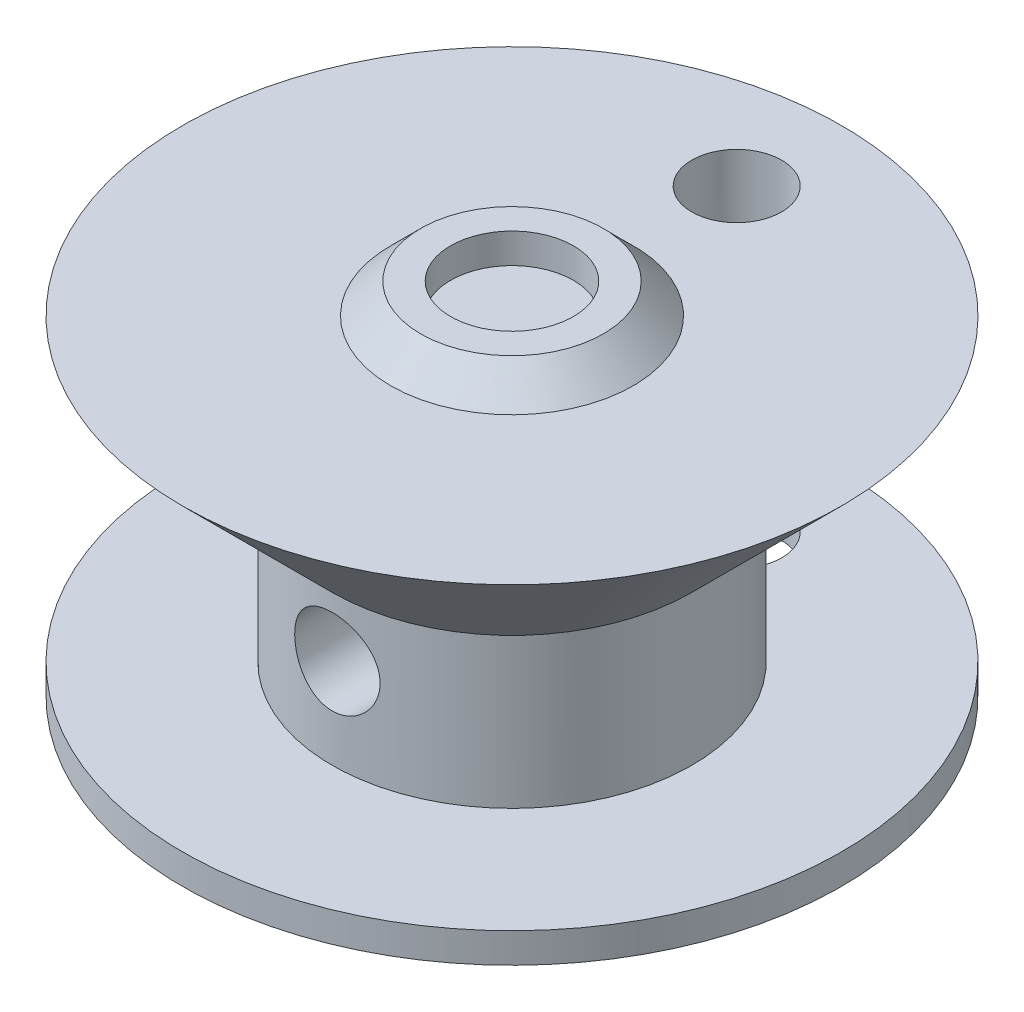
SolidWorks part; units mm, degrees
material "ABS"
ref_plane "Front Plane" through (0, 0, 0) normal (0, 0, 1) x (1, 0, 0)
ref_plane "Top Plane" through (0, 0, 0) normal (0, 1, 0) x (1, 0, 0)
ref_plane "Right Plane" through (0, 0, 0) normal (1, 0, 0) x (0, 0, -1)
sketch "Sketch1" plane through (0, 0, 0) normal (1, 0, 0) x (0, 0, -1)
  line L0 (0, 6) -> (-11, 6) construction
  line L1 (0, 0) -> (0, 18.3424) construction
  line L2 (-11, 6) -> (-11, -6) construction
  line L3 (-11, -6) -> (0, -6) construction
  line L4 (0, -6) -> (0, 6) construction
  line L5 (-11, 6) -> (-11, 5)
  line L7 (-6, 0) -> (-6, -5)
  line L9 (-11, -5) -> (-11, -6)
  line L10 (-11, -6) -> (0, -6) construction
  line L11 (0, -6) -> (0, 6) construction
  line L12 (0, 6) -> (-11, 6) construction
  line L13 (-11, 5) -> (-6, 0)
  line L14 (-6, 0) -> (-6, 6) construction
  line L15 (-11, -5) -> (-6, -5)
  line L16 (-11, 6) -> (-2, 6)
  line L17 (2, -6) -> (-2, -6) construction
  line L18 (2, -6) -> (2, 6) construction
  line L19 (2, 6) -> (-2, 6) construction
  line L20 (-2, -6) -> (-2, 6) construction
  line L21 (2, -6) -> (-2, 6) construction
  line L22 (2, 6) -> (-2, -6) construction
  line L23 (-2.05, 5) -> (2.05, 5) construction
  line L24 (-2.05, 5) -> (-2.05, 7) construction
  line L25 (-2.05, 7) -> (2.05, 7) construction
  line L26 (2.05, 5) -> (2.05, 7) construction
  line L27 (-2.05, 5) -> (2.05, 7) construction
  line L28 (-2.05, 7) -> (2.05, 5) construction
  line L30 (-2.05, 5) -> (0, 5)
  line L31 (0, 5) -> (0, -6) construction
  line L33 (-2, 2) -> (-2, -6)
  line L34 (-2, -6) -> (-11, -6)
  line L35 (-2, 2) -> (0, 4)
  line L36 (0, 4) -> (0, 5)
  line L37 (-2.05, 5) -> (-2.05, 6)
  line L38 (-2.05, 6) -> (-2, 6)
  point P3 (0, 0)
  point P16 (0, 0)
  dimension "D1" = 22
  dimension "D2" = 8
  dimension "D3" = 45
  dimension "D4" = 1
  dimension "D5" = 5
  dimension "D6" = 4
  dimension "D7" = 4
  dimension "D8" = 4.1
  dimension "D9" = 1
  dimension "D10" = 45
  dimension "D11" = 12
revolve "Spool Solid" add sketch "Sketch1" angle 360 about L1 region at (0, 0.7664, 5.0692)
sketch "Sketch2" plane through (0, -6, 0) normal (0, -1, 0) x (1, 0, 0)
  line L0 (1.3229, 1.5) -> (-1.3229, 1.5)
  circle A2 centre (0, 0) radius 2 construction
  circle A3 centre (0, 0) radius 2 construction
  arc A4 (1.3229, 1.5) -> (-1.3229, 1.5) centre (0, 0) ccw
  point P0 (0, -2)
  point P3 (0, 1.5)
  dimension "D1" = 3.5
extrude "Flat Grove Extrude" add sketch "Sketch2" against normal up to next
sketch "Sketch5" plane through (0, -5, 0) normal (0, 1, 0) x (1, 0, 0)
  line L0 (0, 6) -> (0, 11) construction
  circle A0 centre (0, 7.5) radius 1.5
  circle A1 centre (0, 0) radius 6 construction
  circle A2 centre (0, 0) radius 11 construction
  dimension "D1" = 3
extrude "Wire Hole Cut" cut sketch "Sketch5" against normal through all both and the other way through all
sketch "Sketch6" plane through (0, 0, 1.5) normal (0, 0, -1) x (-1, 0, 0)
  line L0 (0, -6) -> (0, 2) construction
  line L1 (1.3229, -6) -> (-1.3229, -6) construction
  circle A0 centre (0, -2) radius 1.425
  dimension "D2" = 2.85
  dimension "D1" = 8
extrude "Set Screw Cut" cut sketch "Sketch6" against normal through all
sketch "Sketch8" plane through (0, 6, 0) normal (0, 1, 0) x (1, 0, 0)
  circle A1 centre (0, 0) radius 11
  circle A4 centre (0, 0) radius 11 construction
  circle A6 centre (0, 0) radius 3.05
  circle A7 centre (0, 0) radius 3.05
  dimension "D1" = 1
extrude "Magnet Holder Trim" cut sketch "Sketch8" against normal blind 1
chamfer "Magnet Holder Chamfer" distance 1 angle 45 1 edges at (0, 5, 3.05)
sketch "Sketch9" plane through (0, -6, 0) normal (0, -1, 0) x (1, 0, 0)
  line L2 (1.3964, 1.7) -> (-1.3964, 1.7)
  line L3 (1.3964, 1.7) -> (-1.3964, 1.7)
  arc A2 (-1.3964, 1.7) -> (1.3964, 1.7) centre (0, 0) ccw
  arc A3 (-1.3964, 1.7) -> (1.3964, 1.7) centre (0, 0) ccw
  dimension "D1" = 0.2
extrude "Axle Tolerance Cut" cut sketch "Sketch9" against normal up to vertex (8 mm away) up to point (1.3229, 2, 1.5)
